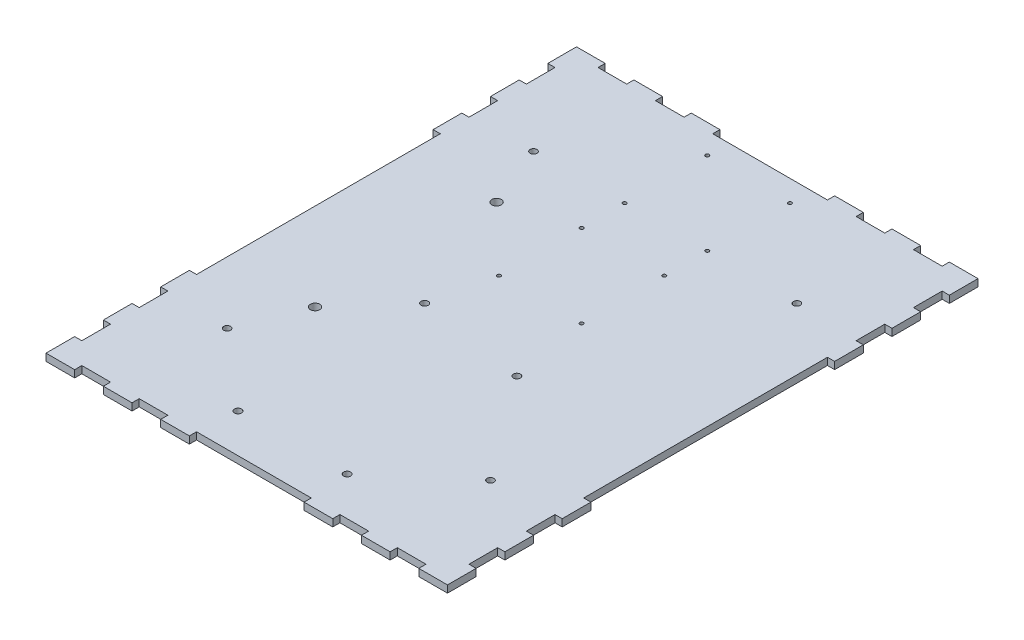
SolidWorks part; units mm, degrees
material "Acrylic (Medium-high impact)"
ref_plane "Front Plane" through (0, 0, 0) normal (0, 0, 1) x (1, 0, 0)
ref_plane "Top Plane" through (0, 0, 0) normal (0, 1, 0) x (1, 0, 0)
ref_plane "Right Plane" through (0, 0, 0) normal (1, 0, 0) x (0, 0, -1)
sketch "Sketch1" plane through (0, 0, 0) normal (0, 1, 0) x (1, 0, 0)
  line L0 (0, 209.55) -> (0, 196.85)
  line L1 (0, 0) -> (177.8, 0)
  line L2 (0, 0) -> (0, 234.95)
  line L3 (0, 234.95) -> (177.8, 234.95)
  line L4 (177.8, 0) -> (177.8, 234.95)
  line L5 (0, 234.95) -> (3.175, 234.95)
  line L6 (0, 234.95) -> (0, 0)
  line L7 (0, 0) -> (3.175, 0)
  line L8 (3.175, 234.95) -> (3.175, 0)
  line L9 (177.8, 234.95) -> (174.625, 234.95)
  line L10 (177.8, 234.95) -> (177.8, 0)
  line L11 (177.8, 0) -> (174.625, 0)
  line L12 (174.625, 234.95) -> (174.625, 0)
  line L13 (0, 234.95) -> (3.175, 234.95)
  line L14 (0, 234.95) -> (0, 222.25)
  line L15 (0, 222.25) -> (3.175, 222.25)
  line L16 (3.175, 234.95) -> (3.175, 222.25)
  line L17 (0, 209.55) -> (3.175, 209.55)
  line L18 (3.175, 209.55) -> (3.175, 196.85)
  line L19 (0, 196.85) -> (3.175, 196.85)
  line L20 (0, 184.15) -> (0, 171.45)
  line L21 (0, 184.15) -> (3.175, 184.15)
  line L22 (3.175, 184.15) -> (3.175, 171.45)
  line L23 (0, 171.45) -> (3.175, 171.45)
  line L24 (0, 117.475) -> (177.8, 117.475) construction
  line L25 (88.9, 234.95) -> (88.9, 0) construction
  line L26 (177.8, 171.45) -> (174.625, 171.45)
  line L27 (174.625, 184.15) -> (174.625, 171.45)
  line L28 (177.8, 184.15) -> (174.625, 184.15)
  line L29 (177.8, 184.15) -> (177.8, 171.45)
  line L30 (177.8, 196.85) -> (174.625, 196.85)
  line L31 (174.625, 209.55) -> (174.625, 196.85)
  line L32 (177.8, 209.55) -> (174.625, 209.55)
  line L33 (174.625, 234.95) -> (174.625, 222.25)
  line L34 (177.8, 222.25) -> (174.625, 222.25)
  line L35 (177.8, 234.95) -> (177.8, 222.25)
  line L36 (177.8, 234.95) -> (174.625, 234.95)
  line L37 (177.8, 234.95) -> (177.8, 0)
  line L38 (177.8, 234.95) -> (174.625, 234.95)
  line L39 (177.8, 209.55) -> (177.8, 196.85)
  line L40 (177.8, 25.4) -> (177.8, 38.1)
  line L41 (177.8, 0) -> (174.625, 0)
  line L42 (177.8, 0) -> (174.625, 0)
  line L43 (177.8, 0) -> (177.8, 12.7)
  line L44 (177.8, 12.7) -> (174.625, 12.7)
  line L45 (174.625, 0) -> (174.625, 12.7)
  line L46 (177.8, 25.4) -> (174.625, 25.4)
  line L47 (174.625, 25.4) -> (174.625, 38.1)
  line L48 (177.8, 38.1) -> (174.625, 38.1)
  line L49 (177.8, 50.8) -> (177.8, 63.5)
  line L50 (177.8, 50.8) -> (174.625, 50.8)
  line L51 (174.625, 50.8) -> (174.625, 63.5)
  line L52 (177.8, 63.5) -> (174.625, 63.5)
  line L53 (0, 63.5) -> (3.175, 63.5)
  line L54 (3.175, 50.8) -> (3.175, 63.5)
  line L55 (0, 50.8) -> (3.175, 50.8)
  line L56 (0, 50.8) -> (0, 63.5)
  line L57 (0, 38.1) -> (3.175, 38.1)
  line L58 (3.175, 25.4) -> (3.175, 38.1)
  line L59 (0, 25.4) -> (3.175, 25.4)
  line L60 (3.175, 0) -> (3.175, 12.7)
  line L61 (0, 12.7) -> (3.175, 12.7)
  line L62 (0, 0) -> (0, 12.7)
  line L63 (0, 0) -> (3.175, 0)
  line L64 (177.8, 0) -> (174.625, 0)
  line L65 (0, 0) -> (3.175, 0)
  line L66 (0, 0) -> (177.8, 0)
  line L67 (0, 25.4) -> (0, 38.1)
  dimension "D1" = 234.95
  dimension "D2" = 177.8
  dimension "D3" = 3.175
  dimension "D4" = 3.175
  dimension "D5" = 12.7
  dimension "D6" = 3.175
  dimension "D7" = 3
extrude "Boss-Extrude1" add sketch "Sketch1" along normal blind 3.175 contours L6 L55 L8 L53 | L6 L59 L8 L57 | L61 L2 L1 L8 | L6 L23 L8 L21 | L0 L19 L8 L17 | L6 L15 L8 L3 | L4 L44 L12 L1 | L37 L48 L12 L46 | L37 L52 L12 L50 | L34 L10 L3 L12 | L10 L32 L12 L30 | L10 L28 L12 L26 | L52 L12 L26 L27 L28 L30 L31 L32 L34 L33 L3 L8 L1 L45 L44 L46 L47 L48 L50 L51 region at (1.5875, 0, -203.2) region at (1.5875, 0, -228.6) region at (88.9, 0, -117.475) region at (1.5875, 0, -177.8) region at (1.5875, 0, -57.15) region at (176.2125, 0, -228.6) region at (1.5875, 0, -31.75) region at (176.2125, 0, -203.2) region at (1.5875, 0, -6.35) region at (176.2125, 0, -177.8) region at (176.2125, 0, -57.15) region at (176.2125, 0, -6.35) region at (176.2125, 0, -31.75)
sketch "Sketch2" plane through (0, 3.175, 0) normal (0, 1, 0) x (1, 0, 0)
  line L0 (3.175, 12.7) -> (30.5816, 12.7)
  line L1 (30.5816, 0) -> (30.5816, 234.95)
  line L3 (0, 0) -> (177.8, 0) construction
  line L4 (0, 234.95) -> (177.8, 234.95) construction
  line L5 (30.5816, 0) -> (30.5816, 14.0716)
  line L6 (30.5816, 14.0716) -> (30.5816, 49.6316)
  line L7 (3.175, 117.475) -> (174.625, 117.475) construction
  line L8 (3.175, 171.45) -> (3.175, 63.5) construction
  line L9 (174.625, 171.45) -> (174.625, 63.5) construction
  line L10 (88.9, 234.95) -> (88.9, 0) construction
  circle A0 centre (30.5816, 49.6316) radius 1.524
  circle A1 centre (147.2184, 49.6316) radius 1.524
  circle A2 centre (147.2184, 185.3184) radius 1.524
  circle A3 centre (30.5816, 185.3184) radius 1.524
  dimension "D4" = 3.048
  dimension "D1" = 27.4066
  dimension "D2" = 14.0716
  dimension "D3" = 35.56
extrude "Cut-Extrude1" cut sketch "Sketch2" against normal blind 3.175 and the other way through all contours A3 L1 | A3 L1 | L1 A0 L6 | L6 A0 L1 | A1 | A2 region at (29.9348, 3.175, -49.6316) region at (29.9348, 3.175, -185.3184) region at (31.2284, 3.175, -185.3184) region at (31.2284, 3.175, -49.6316) region at (147.2184, 3.175, -49.6316) region at (147.2184, 3.175, -185.3184)
sketch "Sketch3" plane through (0, 3.175, 0) normal (0, 1, 0) x (1, 0, 0)
  line L0 (88.9, 234.95) -> (88.9, 0) construction
  line L1 (0, 234.95) -> (177.8, 234.95) construction
  line L2 (0, 0) -> (177.8, 0) construction
  line L4 (88.9, 234.95) -> (70.6, 234.95)
  line L5 (88.9, 234.95) -> (88.9, 222.25)
  line L6 (88.9, 222.25) -> (70.6, 222.25)
  line L7 (70.6, 234.95) -> (70.6, 222.25)
  line L8 (70.6, 222.25) -> (107.2, 222.25)
  line L9 (70.6, 222.25) -> (70.6, 185.65)
  line L10 (70.6, 185.65) -> (107.2, 185.65)
  line L11 (107.2, 222.25) -> (107.2, 185.65)
  line L12 (70.6, 166.6) -> (107.2, 166.6)
  line L13 (70.6, 166.6) -> (70.6, 130)
  line L14 (70.6, 130) -> (107.2, 130)
  line L15 (107.2, 166.6) -> (107.2, 130)
  circle A0 centre (70.6, 222.25) radius 0.8
  circle A1 centre (107.2, 222.25) radius 0.8
  circle A2 centre (70.6, 185.65) radius 0.8
  circle A3 centre (107.2, 185.65) radius 0.8
  circle A4 centre (70.6, 166.6) radius 0.8
  circle A5 centre (107.2, 166.6) radius 0.8
  circle A6 centre (70.6, 130) radius 0.8
  circle A7 centre (107.2, 130) radius 0.8
  dimension "D4" = 1.6
  dimension "D5" = 1.6
  dimension "D6" = 1.6
  dimension "D7" = 1.6
  dimension "D8" = 36.6
  dimension "D10" = 1.6
  dimension "D11" = 1.6
  dimension "D12" = 1.6
  dimension "D13" = 1.6
  dimension "D1" = 12.7
  dimension "D2" = 18.3
  dimension "D3" = 36.6
  dimension "D9" = 19.05
extrude "Cut-Extrude2" cut sketch "Sketch3" against normal blind 5.715 contours L8 A0 L7 | L7 A0 L9 | L9 A0 L8 | L8 A1 L11 | L11 A1 L8 | L10 A2 L9 | L9 A2 L10 | L11 A3 L10 | L10 A3 L11 | L13 A4 L12 | L12 A4 L13 | L12 A5 L15 | L15 A5 L12 | L14 A6 L13 | L13 A6 L14 | L15 A7 L14 | L14 A7 L15 region at (70.9395, 3.175, -222.5895) region at (70.2605, 3.175, -222.25) region at (70.9395, 3.175, -221.9105) region at (107.3132, 3.175, -222.3632) region at (106.8605, 3.175, -221.9105) region at (70.9395, 3.175, -185.9895) region at (70.4868, 3.175, -185.5368) region at (107.3132, 3.175, -185.5368) region at (106.8605, 3.175, -185.9895) region at (70.4868, 3.175, -166.7132) region at (70.9395, 3.175, -166.2605) region at (107.3132, 3.175, -166.7132) region at (106.8605, 3.175, -166.2605) region at (70.9395, 3.175, -130.3395) region at (70.4868, 3.175, -129.8868) region at (107.3132, 3.175, -129.8868) region at (106.8605, 3.175, -130.3395)
sketch "Sketch4" plane through (0, 3.175, 0) normal (0, 1, 0) x (1, 0, 0)
  line L0 (88.9, 0) -> (88.9, 20.32) construction
  line L1 (0, 0) -> (177.8, 0) construction
  line L2 (88.9, 20.32) -> (64.7319, 20.32) construction
  line L3 (64.7319, 20.32) -> (64.7319, 95.4532) construction
  line L4 (64.7319, 20.32) -> (113.0681, 20.32) construction
  line L5 (113.0681, 20.32) -> (113.0681, 102.9462) construction
  circle A0 centre (64.7319, 20.32) radius 1.5621
  circle A3 centre (113.0681, 20.32) radius 1.5621
  circle A4 centre (64.7319, 102.9462) radius 1.5621
  circle A5 centre (113.0681, 95.4532) radius 1.5621
  point P6 (0, 0)
  dimension "D3" = 3.1242
  dimension "D4" = 75.1332
  dimension "D9" = 3.1242
  dimension "D1" = 20.32
  dimension "D2" = 24.1681
  dimension "D6" = 48.3362
  dimension "D7" = 82.6262
extrude "Cut-Extrude3" cut sketch "Sketch4" against normal blind 10.16 contours A3 | A0 | A4 | A5 region at (64.7319, 3.175, -20.32) region at (113.0681, 3.175, -20.32) region at (64.7319, 3.175, -102.9462) region at (113.0681, 3.175, -95.4532)
sketch "Sketch5" plane through (0, 3.175, 0) normal (0, 1, 0) x (1, 0, 0)
  line L0 (88.9, 0) -> (88.9, 18.3402) construction
  line L1 (0, 0) -> (177.8, 0) construction
  line L3 (0, 0) -> (12.7, 0)
  line L4 (0, 0) -> (0, 3.175)
  line L5 (0, 3.175) -> (12.7, 3.175)
  line L6 (12.7, 0) -> (12.7, 3.175)
  line L10 (25.4, 3.175) -> (38.1, 3.175)
  line L11 (25.4, 0) -> (38.1, 0)
  line L12 (38.1, 0) -> (38.1, 3.175)
  line L13 (25.4, 0) -> (25.4, 3.175)
  line L14 (50.8, 3.175) -> (63.5, 3.175)
  line L15 (50.8, 0) -> (63.5, 0)
  line L16 (63.5, 0) -> (63.5, 3.175)
  line L17 (50.8, 0) -> (50.8, 3.175)
  line L18 (0, 3.175) -> (177.8, 3.175)
  line L19 (127, 0) -> (127, 3.175)
  line L20 (114.3, 0) -> (114.3, 3.175)
  line L21 (127, 0) -> (114.3, 0)
  line L22 (127, 3.175) -> (114.3, 3.175)
  line L23 (152.4, 0) -> (152.4, 3.175)
  line L24 (139.7, 0) -> (139.7, 3.175)
  line L25 (152.4, 0) -> (139.7, 0)
  line L26 (152.4, 3.175) -> (139.7, 3.175)
  line L27 (165.1, 0) -> (165.1, 3.175)
  line L28 (177.8, 3.175) -> (165.1, 3.175)
  line L29 (177.8, 0) -> (177.8, 3.175)
  line L30 (177.8, 0) -> (165.1, 0)
  line L63 (0, 63.5) -> (0, 50.8)
  line L64 (0, 50.8) -> (3.175, 50.8)
  line L65 (3.175, 50.8) -> (3.175, 38.1)
  line L66 (3.175, 38.1) -> (0, 38.1)
  line L67 (0, 38.1) -> (0, 25.4)
  line L68 (0, 25.4) -> (3.175, 25.4)
  line L69 (3.175, 25.4) -> (3.175, 12.7)
  line L70 (3.175, 12.7) -> (0, 12.7)
  line L71 (0, 12.7) -> (0, 0)
  line L72 (0, 0) -> (177.8, 0)
  line L73 (177.8, 0) -> (177.8, 12.7)
  line L74 (177.8, 12.7) -> (174.625, 12.7)
  line L75 (174.625, 12.7) -> (174.625, 25.4)
  line L76 (174.625, 25.4) -> (177.8, 25.4)
  line L77 (177.8, 25.4) -> (177.8, 38.1)
  line L78 (177.8, 38.1) -> (174.625, 38.1)
  line L79 (174.625, 38.1) -> (174.625, 50.8)
  line L80 (174.625, 50.8) -> (177.8, 50.8)
  line L81 (177.8, 50.8) -> (177.8, 63.5)
  line L82 (177.8, 63.5) -> (174.625, 63.5)
  line L83 (174.625, 63.5) -> (174.625, 171.45)
  line L84 (174.625, 171.45) -> (177.8, 171.45)
  line L85 (177.8, 171.45) -> (177.8, 184.15)
  line L86 (177.8, 184.15) -> (174.625, 184.15)
  line L87 (174.625, 184.15) -> (174.625, 196.85)
  line L88 (174.625, 196.85) -> (177.8, 196.85)
  line L89 (177.8, 196.85) -> (177.8, 209.55)
  line L90 (177.8, 209.55) -> (174.625, 209.55)
  line L91 (174.625, 209.55) -> (174.625, 222.25)
  line L92 (174.625, 222.25) -> (177.8, 222.25)
  line L93 (177.8, 222.25) -> (177.8, 234.95)
  line L94 (177.8, 234.95) -> (0, 234.95)
  line L95 (0, 234.95) -> (0, 222.25)
  line L96 (0, 222.25) -> (3.175, 222.25)
  line L97 (3.175, 222.25) -> (3.175, 209.55)
  line L98 (3.175, 209.55) -> (0, 209.55)
  line L99 (0, 209.55) -> (0, 196.85)
  line L100 (0, 196.85) -> (3.175, 196.85)
  line L101 (3.175, 196.85) -> (3.175, 184.15)
  line L102 (3.175, 184.15) -> (0, 184.15)
  line L103 (0, 184.15) -> (0, 171.45)
  line L104 (0, 171.45) -> (3.175, 171.45)
  line L105 (3.175, 171.45) -> (3.175, 63.5)
  line L106 (3.175, 63.5) -> (0, 63.5)
  line L107 (0, 63.5) -> (0, 50.8)
  line L108 (0, 50.8) -> (3.175, 50.8)
  line L109 (3.175, 50.8) -> (3.175, 38.1)
  line L110 (3.175, 38.1) -> (0, 38.1)
  line L111 (0, 38.1) -> (0, 25.4)
  line L112 (0, 25.4) -> (3.175, 25.4)
  line L113 (3.175, 25.4) -> (3.175, 12.7)
  line L114 (3.175, 12.7) -> (0, 12.7)
  line L115 (0, 12.7) -> (0, 0)
  line L116 (0, 0) -> (177.8, 0)
  line L117 (177.8, 0) -> (177.8, 12.7)
  line L118 (177.8, 12.7) -> (174.625, 12.7)
  line L119 (174.625, 12.7) -> (174.625, 25.4)
  line L120 (174.625, 25.4) -> (177.8, 25.4)
  line L121 (177.8, 25.4) -> (177.8, 38.1)
  line L122 (177.8, 38.1) -> (174.625, 38.1)
  line L123 (174.625, 38.1) -> (174.625, 50.8)
  line L124 (174.625, 50.8) -> (177.8, 50.8)
  line L125 (177.8, 50.8) -> (177.8, 63.5)
  line L126 (177.8, 63.5) -> (174.625, 63.5)
  line L127 (174.625, 63.5) -> (174.625, 171.45)
  line L128 (174.625, 171.45) -> (177.8, 171.45)
  line L129 (177.8, 171.45) -> (177.8, 184.15)
  line L130 (177.8, 184.15) -> (174.625, 184.15)
  line L131 (174.625, 184.15) -> (174.625, 196.85)
  line L132 (174.625, 196.85) -> (177.8, 196.85)
  line L133 (177.8, 196.85) -> (177.8, 209.55)
  line L134 (177.8, 209.55) -> (174.625, 209.55)
  line L135 (174.625, 209.55) -> (174.625, 222.25)
  line L136 (174.625, 222.25) -> (177.8, 222.25)
  line L137 (177.8, 222.25) -> (177.8, 234.95)
  line L138 (177.8, 234.95) -> (0, 234.95)
  line L139 (0, 234.95) -> (0, 222.25)
  line L140 (0, 222.25) -> (3.175, 222.25)
  line L141 (3.175, 222.25) -> (3.175, 209.55)
  line L142 (3.175, 209.55) -> (0, 209.55)
  line L143 (0, 209.55) -> (0, 196.85)
  line L144 (0, 196.85) -> (3.175, 196.85)
  line L145 (3.175, 196.85) -> (3.175, 184.15)
  line L146 (3.175, 184.15) -> (0, 184.15)
  line L147 (0, 184.15) -> (0, 171.45)
  line L148 (0, 171.45) -> (3.175, 171.45)
  line L149 (3.175, 171.45) -> (3.175, 63.5)
  line L150 (3.175, 63.5) -> (0, 63.5)
  point P22 (88.9, 3.175)
  dimension "D1" = 3.175
  dimension "D2" = 12.7
  dimension "D4" = 0
  dimension "D3" = 3
extrude "Cut-Extrude4" cut sketch "Sketch5" against normal blind 7.62 contours L6 L116 L13 L18 | L12 L116 L17 L18 | L116 L0 L18 L16 | L0 L116 L20 L18 | L19 L116 L24 L18 | L23 L116 L27 L18 region at (76.2, 3.175, -1.5875) region at (101.6, 3.175, -1.5875) region at (44.45, 3.175, -1.5875) region at (133.35, 3.175, -1.5875) region at (19.05, 3.175, -1.5875) region at (158.75, 3.175, -1.5875)
ref_plane "Plane2" through (0, 0, -117.475) normal (0, 0, 1) x (1, 0, 0)
mirror "Mirror1" about plane through (0, 0, -117.475) normal (0, 0, 1) of "Cut-Extrude4"
sketch "Sketch7" plane through (0, 0, 0) normal (0, -1, 0) x (1, 0, 0)
  line L0 (3.175, -117.475) -> (41.8719, -117.475) construction
  line L1 (3.175, -171.45) -> (3.175, -63.5) construction
  line L2 (41.8719, -3.175) -> (41.8719, -231.775) construction
  line L3 (38.1, -3.175) -> (50.8, -3.175) construction
  line L4 (38.1, -231.775) -> (50.8, -231.775) construction
  circle A0 centre (64.7319, -102.9462) radius 1.5621 construction
  circle A1 centre (41.8719, -77.2795) radius 2.0955
  circle A2 centre (41.8719, -157.6705) radius 2.0955
  dimension "D2" = 4.191
  dimension "D1" = 22.86
  dimension "D3" = 40.1955
extrude "Cut-Extrude5" cut sketch "Sketch7" against normal blind 7.62
